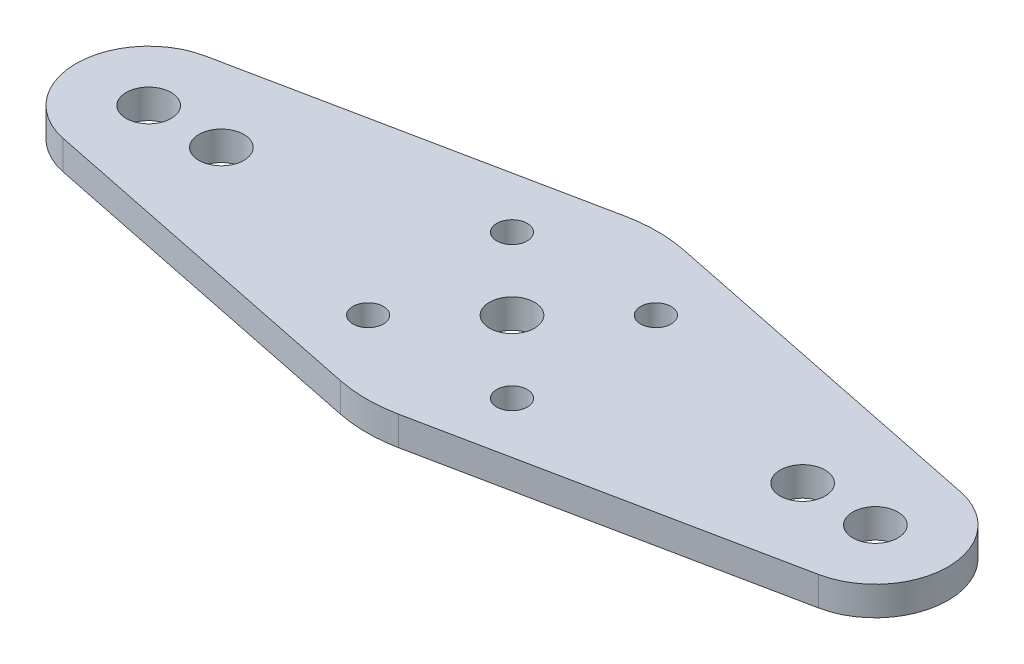
SolidWorks part; units mm, degrees
note: The reader was unsure of these and kept them because the rebuilt part matched: thickness of "Базовая кромка1", "Листовой металл3", "Листовой металл4".
material "Ст 3 ГОСТ 380-88"
ref_plane "Спереди" through (0, 0, 0) normal (0, 0, 1) x (1, 0, 0)
ref_plane "Сверху" through (0, 0, 0) normal (0, 1, 0) x (1, 0, 0)
ref_plane "Справа" through (0, 0, 0) normal (1, 0, 0) x (0, 0, -1)
other "Configuration Table"
sketch "Эскиз1" plane through (0, 0, 0) normal (0, 1, 0) x (1, 0, 0)
  line L0 (0, 0) -> (-4.719, 0) construction
  line L5 (0, 0) -> (-9.8995, -9.8995) construction
  line L6 (0, 0) -> (0, 20) construction
  line L7 (0, 0) -> (9.8995, 9.8995) construction
  line L8 (-52, 9.798) -> (-4, 19.5959)
  line L9 (4, 19.5959) -> (52, 9.798)
  line L10 (52, -9.798) -> (4, -19.5959)
  line L11 (-4, -19.5959) -> (-52, -9.798)
  circle A0 centre (9.8995, 9.8995) radius 2.1
  arc A1 (0, 20) -> (-4, 19.5959) centre (0, 0) ccw construction
  circle A2 centre (9.8995, -9.8995) radius 2.1
  circle A3 centre (-9.8995, -9.8995) radius 2.1
  circle A4 centre (-9.8995, 9.8995) radius 2.1
  circle A5 centre (50, 0) radius 3.1
  circle A6 centre (-50, 0) radius 3.1
  arc A7 (-52, 9.798) -> (-52, -9.798) centre (-50, 0) ccw
  arc A8 (52, -9.798) -> (52, 9.798) centre (50, 0) ccw
  arc A9 (-4, -19.5959) -> (4, -19.5959) centre (0, 0) ccw
  arc A10 (-4, -19.5959) -> (4, -19.5959) centre (0, 0) ccw construction
  arc A11 (4, 19.5959) -> (-4, 19.5959) centre (0, 0) ccw
  circle A12 centre (-40, 0) radius 3.1
  circle A13 centre (40, 0) radius 3.1
  point P0 (0, 0)
  point P20 (0, 0)
  dimension "D3" = 4.2
  dimension "D7" = 6.2
  dimension "D11" = 20
  dimension "D12" = 20
  dimension "D13" = 40
  dimension "D14" = 40
  dimension "D2" = 14
  dimension "D4" = 14
  dimension "D5" = 45
  dimension "D9" = 50
  dimension "D10" = 50
  dimension "D15" = 40
  dimension "D17" = 14
  dimension "D6" = 4
base flange "Базовая кромка1" sketch "Эскиз1" thickness 4 reverse thickness direction no parameters "D1"=2
sketch "Эскиз6" plane through (0, 0, 0) normal (0, 1, 0) x (1, 0, 0)
  circle A0 centre (0, 0) radius 3.1
  dimension "D1" = 6.2
extrude "Вырез-Вытянуть1" cut sketch "Эскиз6" against normal blind 10 normal cut yes
sketch "Сгиб-Линии1" [suppressed] plane through (0, 0, 0) normal (0, 1, 0) x (1, 0, 0)
sketch "Граничная рамка1" [suppressed] plane through (0, 0, 0) normal (0, 1, 0) x (1, 0, 0)
sheet metal parameters "Листовой металл3" thickness 4 parameters "D1"=2, "D7"=3
flat pattern "Развертка3" [suppressed]
sketch "Сгиб-Линии2" plane through (0, 0, 0) normal (0, 1, 0) x (1, 0, 0)
sketch "Граничная рамка2" [suppressed] plane through (0, 0, 0) normal (0, 1, 0) x (1, 0, 0)
sheet metal parameters "Листовой металл4" thickness 4 parameters "D1"=2, "D7"=3
flat pattern "Развертка3"
sketch "Сгиб-Линии2" plane through (0, 0, 0) normal (0, 1, 0) x (1, 0, 0)
sketch3d "Граничная рамка2" [suppressed]
  line L0 (-61.7979, -7.798, 0) -> (53.7979, -31.3939, 0) construction
  line L1 (-53.7979, 31.3939, 0) -> (61.7979, 7.798, 0) construction
  line L2 (-61.7979, -7.798, 0) -> (-53.7979, 31.3939, 0) construction
  line L3 (53.7979, -31.3939, 0) -> (61.7979, 7.798, 0) construction
